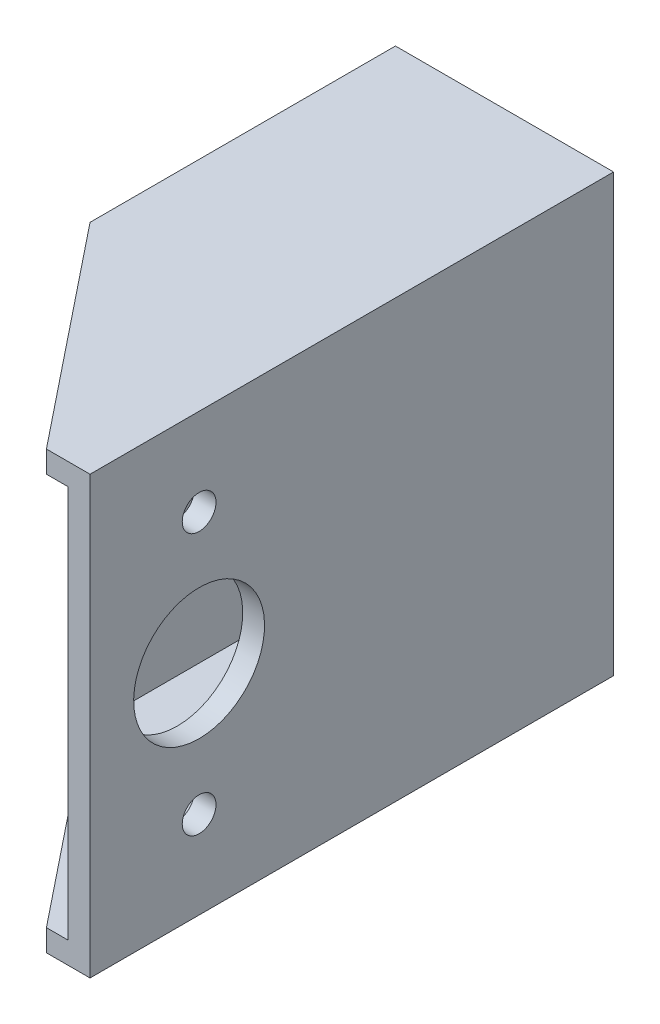
SolidWorks part; units mm, degrees
ref_plane "Front Plane" through (0, 0, 0) normal (0, 0, 1) x (1, 0, 0)
ref_plane "Top Plane" through (0, 0, 0) normal (0, 1, 0) x (1, 0, 0)
ref_plane "Right Plane" through (0, 0, 0) normal (1, 0, 0) x (0, 0, -1)
sketch "Sketch1" plane through (0, 0, 0) normal (0, 0, 1) x (1, 0, 0)
  line L1 (-12.1647, 2.5103) -> (19.5853, 2.5103)
  line L2 (-12.1647, 2.5103) -> (-12.1647, -60.9897)
  line L3 (-12.1647, -60.9897) -> (19.5853, -60.9897)
  line L4 (19.5853, 2.5103) -> (19.5853, -60.9897)
  line L5 (-8.9897, -0.6647) -> (16.4103, -0.6647)
  line L6 (-8.9897, -0.6647) -> (-8.9897, -57.8147)
  line L7 (-8.9897, -57.8147) -> (16.4103, -57.8147)
  line L8 (16.4103, -0.6647) -> (16.4103, -57.8147)
  dimension "D1" = 63.5
  dimension "D2" = 31.75
  dimension "D3" = 3.175
  dimension "D4" = 3.175
  dimension "D5" = 3.175
  dimension "D6" = 3.175
extrude "Boss-Extrude1" add sketch "Sketch1" along normal blind 76.2
sketch "Sketch2" plane through (0, 2.5103, 0) normal (0, 1, 0) x (1, 0, 0)
  line L0 (13.2353, -76.2) -> (-12.1647, -44.45)
  line L1 (19.5853, -76.2) -> (-12.1647, -76.2) construction
  line L2 (-12.1647, -76.2) -> (-12.1647, 0) construction
  line L3 (-12.1647, -44.45) -> (-12.1647, -76.2)
  line L4 (-12.1647, -76.2) -> (13.2353, -76.2)
  line L5 (13.2353, -76.2) -> (13.5724, -152.4399)
  line M4 (-12.1647, 0) -> (-12.1647, -76.2)
  line M5 (-12.1647, -76.2) -> (19.5853, -76.2)
  dimension "D1" = 31.75
  dimension "D2" = 25.4
extrude "Cut-Extrude1" cut sketch "Sketch2" against normal up to surface (63.5 mm away) contours L0 M5 M4 region at (-3.6981, 2.5103, 65.6167) up to face at (3.7103, -60.9897, 38.1)
sketch "Sketch3" plane through (16.4103, 0, 0) normal (-1, 0, 0) x (0, 0, 1)
  line L0 (76.2, -57.8147) -> (76.2, -0.6647) construction
  line L1 (44.45, -60.9897) -> (76.2, -60.9897) construction
  line L2 (76.2, -29.2397) -> (48.4187, -29.2397)
  line L3 (48.4187, -57.8147) -> (48.4187, -0.6647) construction
  circle A0 centre (60.325, -29.2397) radius 9.525
  point P0 (60.325, -48.2897)
  point P9 (60.325, -10.1897)
  dimension "D3" = 15.875
  dimension "D4" = 19.05
  dimension "D1" = 15.875
  dimension "D2" = 12.7
extrude "Cut-Extrude2" cut sketch "Sketch3" against normal up to surface (3.175 mm away) contours A0 up to face at (19.5853, -29.2397, 38.1)
hole_wizard "#10 (0.1935) Diameter Hole1" positions "3DSketch1" profile "Sketch4" hole size "#10" standard "ANSI Inch" end condition through all
sketch3d "3DSketch1"
  point P0 (16.4103, -48.2897, 60.325)
  point P3 (16.4103, -10.1897, 60.325)
sketch "Sketch4" plane through (16.4103, -48.2897, 60.325) normal (0, 1, 0) x (0, 0, 1)
  line L0 (0, 0) -> (0, 3.175)
  line L1 (0, 3.175) -> (2.4574, 3.175)
  line L2 (2.4574, 3.175) -> (2.4574, 0)
  line L5 (2.4574, 0) -> (0, 0)
  line L11 (0, -6.35) -> (0, 107.95) construction
  dimension "Thru Hole Dia." = 4.9149
  dimension "Thru Hole Depth" = 3.175
